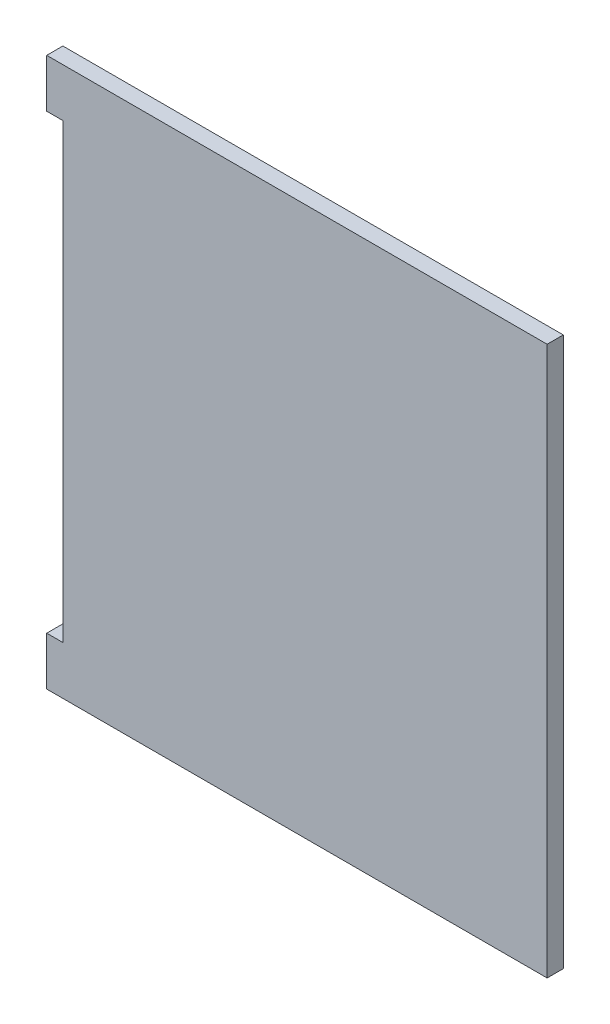
SolidWorks part; units mm, degrees
ref_plane "Front" through (0, 0, 0) normal (0, 0, 1) x (1, 0, 0)
ref_plane "Top" through (0, 0, 0) normal (0, 1, 0) x (1, 0, 0)
ref_plane "Right" through (0, 0, 0) normal (1, 0, 0) x (0, 0, -1)
sketch "Sketch1" plane through (0, 0, 0) normal (0, 0, 1) x (1, 0, 0)
  line L1 (0, 0) -> (196.85, 0)
  line L2 (0, 0) -> (0, -215.9)
  line L3 (0, -215.9) -> (196.85, -215.9)
  line L4 (196.85, 0) -> (196.85, -215.9)
  dimension "D1" = 196.85
  dimension "D2" = 215.9
extrude "Boss-Extrude1" add sketch "Sketch1" along normal blind 6.35
sketch "Sketch2" plane through (0, 0, 0) normal (0, 0, -1) x (-1, 0, 0)
  line L0 (0, 0) -> (0, -215.9) construction
  line L1 (-6.35, -19.05) -> (0, -19.05)
  line L2 (-6.35, -19.05) -> (-6.35, -196.85)
  line L3 (-6.35, -196.85) -> (0, -196.85)
  line L4 (0, -19.05) -> (0, -196.85)
  line L5 (0, -215.9) -> (-196.85, -215.9) construction
  point P6 (0, -107.95)
  dimension "D1" = 6.35
  dimension "D2" = 19.05
extrude "Cut-Extrude1" cut sketch "Sketch2" against normal through all
